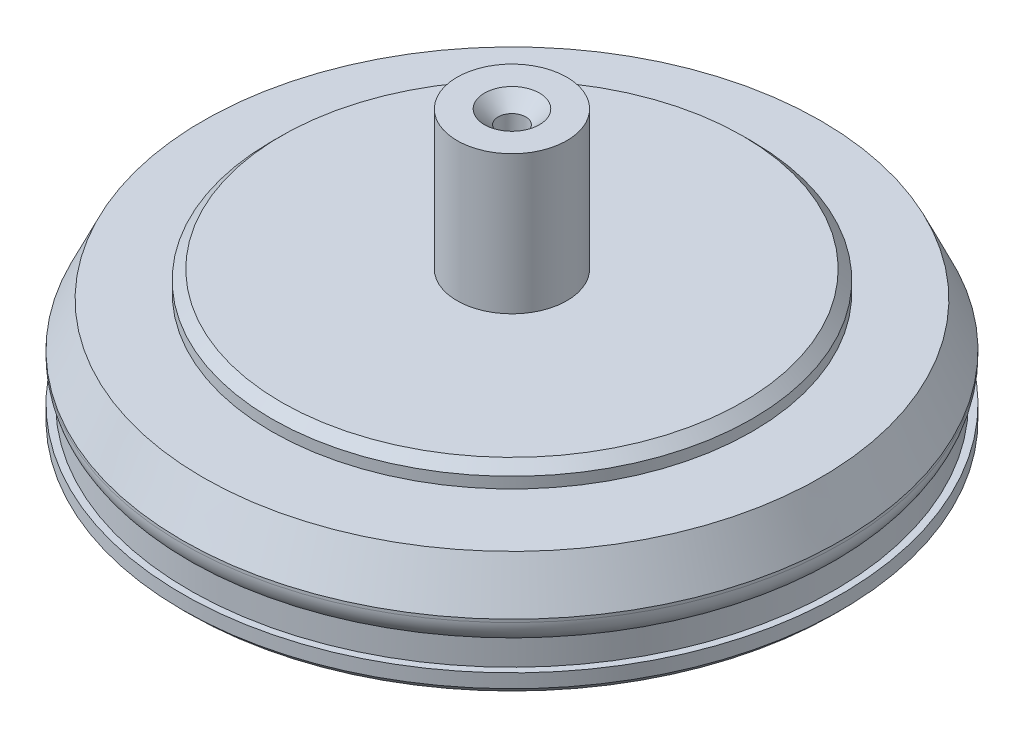
SolidWorks part; units mm, degrees
note: The reader was unsure of these and kept them because the rebuilt part matched: shared geometry of "Sketch3<3>".
material "POLYURETHANE (11671)"
ref_plane "Front Plane" through (0, 0, 0) normal (0, 0, 1) x (1, 0, 0)
ref_plane "Top Plane" through (0, 0, 0) normal (0, 1, 0) x (1, 0, 0)
ref_plane "Right Plane" through (0, 0, 0) normal (1, 0, 0) x (0, 0, -1)
sketch "Sketch1" plane through (0, 0, 0) normal (0, 0, 1) x (1, 0, 0)
  line L0 (0, 0) -> (0, 24.495) construction
  line L1 (-20, 3.2) -> (-20, 6.2)
  line L2 (0, 0) -> (-20, 0)
  line L3 (0, 0) -> (0, 2.5)
  line L4 (0, 2.5) -> (-20, 2.5)
  line L5 (-20, 0) -> (-20, 2.5)
  line L6 (0, 0) -> (-20, 2.5) construction
  line L7 (0, 2.5) -> (-20, 0) construction
  line L8 (-20, 0) -> (-24, 0)
  line L9 (-20, 0) -> (-20, 2.5)
  line L10 (-20, 6.2) -> (-24, 6.2)
  line L11 (-24, 0) -> (-24, 6.2)
  line L12 (-20, 0) -> (-24, 6.2) construction
  line L13 (-20, 6.2) -> (-24, 0) construction
  line L14 (-20, 6.2) -> (-2, 6.2)
  line L15 (-20, 6.2) -> (-20, 3.2)
  line L17 (-2, 6.2) -> (-2, 3.2)
  line L18 (-20, 6.2) -> (-2, 3.2) construction
  line L19 (-20, 3.2) -> (-2, 6.2) construction
  line L20 (-2, 6.2) -> (-4, 6.2)
  line L21 (-2, 6.2) -> (-2, 18.2)
  line L22 (-2, 18.2) -> (-4, 18.2)
  line L23 (-4, 6.2) -> (-4, 18.2)
  line L24 (-2, 6.2) -> (-4, 18.2) construction
  line L25 (-2, 18.2) -> (-4, 6.2) construction
  line L27 (-2, 18.2) -> (-1, 18.2)
  line L28 (-2, 18.2) -> (-2, 14.2)
  line L29 (-2, 14.2) -> (-1, 14.2)
  line L30 (-1, 18.2) -> (-1, 14.2)
  line L31 (-4, 8.1) -> (-17.5, 8.1)
  line L32 (-4, 8.1) -> (-4, 6.6)
  line L33 (-4, 6.6) -> (-17.5, 6.6)
  line L34 (-17.5, 8.1) -> (-17.5, 6.6)
  arc A0 (-20, 3.2) -> (-20, 2.5) centre (-20, 2.85) ccw
  spline S0 degree 3 poles (-20, 3.2) (-17.9808, 2.6825) (-14.9123, 2.8353) (-10.8778, 3.9894) (-6.923, 2.8606) (-3.9364, 2.6737) (-2, 3.2) knots 0 0 0 0 0.336802 0.506831 0.676363 1 1 1 1
  point P6 (-10, 1.25)
  point P10 (-22, 3.1)
  point P14 (-11, 4.7)
  point P19 (-3, 12.2)
  dimension "D1" = 40
  dimension "D2" = 2.5
  dimension "D3" = 4
  dimension "D4" = 3.7
  dimension "D5" = 0.7
  dimension "D6" = 4
  dimension "D7" = 3
  dimension "D8" = 8
  dimension "D9" = 1.2
  dimension "D10" = 10.875
  dimension "D11" = 12
  dimension "D12" = 2
  dimension "D13" = 4
  dimension "D14" = 1.5
  dimension "D15" = 0.4
  dimension "D16" = 35
  dimension "D17" = 0.35
  dimension "D18" = 0.7
  dimension "D19" = 0.7
  dimension "D20" = 0.35
  dimension "D21" = 2.8011
  dimension "D22" = 5.8366
  dimension "D23" = 11.9226
  dimension "D24" = 14.9581
  dimension "D25" = 6.2
revolve "Revolve1" add sketch "Sketch1" angle 360 about L0
chamfer "Chamfer1" distance 1.5 angle 65 2 edges at (0, 6.2, -24) (0, 0, -24)
chamfer "Chamfer2" distance 1 angle 60 1 edges at (0, 6.2, -4)
fillet "Fillet6" radius 2 1 edges at (0, 1.5, -24)
chamfer "Chamfer3" distance 1 angle 45 2 edges at (0, 18.2, -1) (0, 14.2, -2)
chamfer "Chamfer4" distance 0.7 angle 45 1 edges at (0, 8.1, -17.5)
sketch "Sketch3" plane through (0, 0, 0) normal (0, 0, 1) x (1, 0, 0)
  line L0 (-2, 6.2) -> (-2, 3.2) construction
  line L1 (-2, 1) -> (-4, 1)
  line L2 (-2, 1) -> (-2, -0.4)
  line L3 (-2, -0.4) -> (-4, -0.4)
  line L4 (-4, 1) -> (-4, -0.4)
  line L5 (-2, 1) -> (-4, -0.4) construction
  line L6 (-2, -0.4) -> (-4, 1) construction
  line L7 (-4, 6.2) -> (-4, 18.2) construction
  line L8 (0, 0) -> (0, 24.495) construction
  line L9 (-2, -0.4) -> (-24, -0.4)
  line L10 (-2, -0.4) -> (-2, -1.9)
  line L11 (-2, -1.9) -> (-24, -1.9)
  line L12 (-24, -0.4) -> (-24, -1.9)
  line L13 (-2, -0.4) -> (-24, -1.9) construction
  line L14 (-2, -1.9) -> (-24, -0.4) construction
  line L16 (-2, 1) -> (0, 1)
  line L17 (-2, 1) -> (-2, -1.9)
  line L18 (-2, -1.9) -> (0, -1.9)
  line L19 (0, 1) -> (0, -1.9)
  line L20 (-2, 1) -> (0, -1.9) construction
  line L21 (-2, -1.9) -> (0, 1) construction
  line L22 (-23.5, 1.6) -> (-22.8, 1.6)
  line L23 (-23.5, 1.6) -> (-23.5, -0.4)
  line L24 (-23.5, -0.4) -> (-22.8, -0.4)
  line L25 (-22.8, 1.6) -> (-22.8, -0.4)
  line L26 (-23.5, 1.6) -> (-22.8, -0.4) construction
  line L27 (-23.5, -0.4) -> (-22.8, 1.6) construction
  point P4 (-3, 0.3)
  point P14 (-13, -1.15)
  point P21 (-1, -0.45)
  point P25 (-23.15, 0.6)
  dimension "D1" = 1
  dimension "D2" = 1.5
  dimension "D3" = 0.4
  dimension "D4" = 24
  dimension "D5" = 23.5
  dimension "D6" = 2
  dimension "D7" = 0.7
revolve "Revolve2" add sketch "Sketch3" angle 360 about L0
revolve "Revolve3" add sketch "Sketch3<3>" angle 355 about L19
sketch "Sketch3<3>" plane through (0, 0, 0) normal (0, 0, 1) x (1, 0, 0) same geometry as "Sketch3"
chamfer "Chamfer5" distance 0.5 angle 45 1 edges at (0, -1.9, -24)
